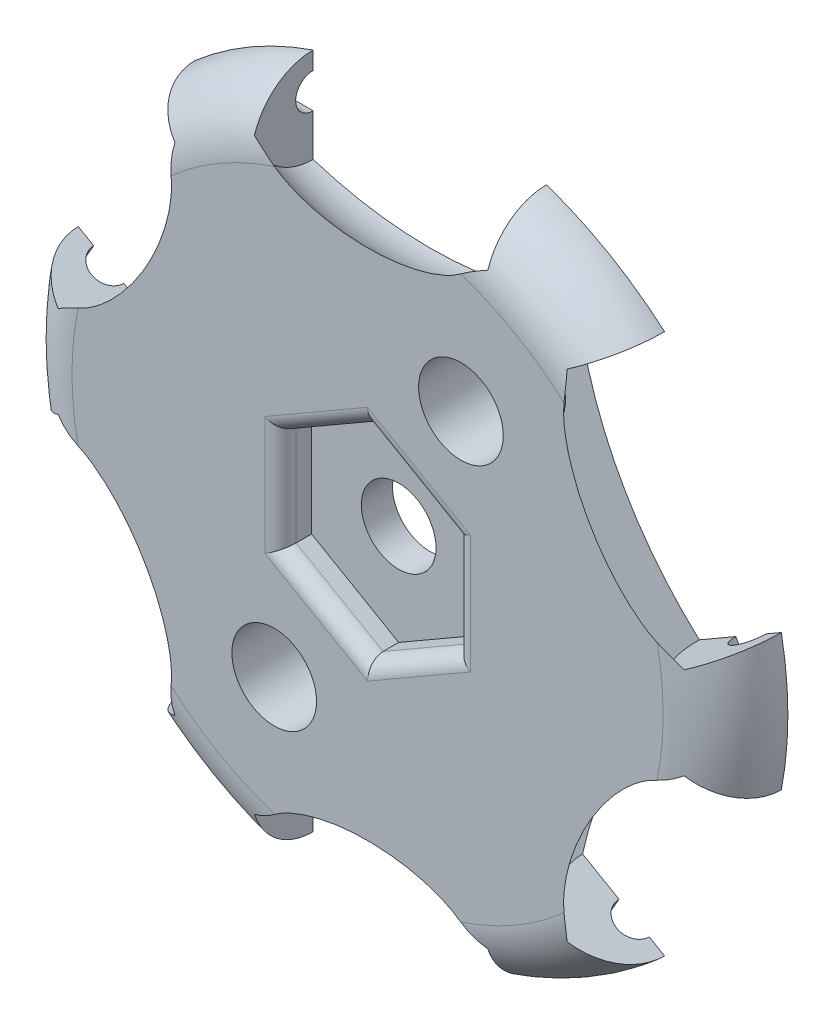
SolidWorks part; units mm, degrees
ref_plane "Front Plane" through (0, 0, 0) normal (0, 0, 1) x (1, 0, 0)
ref_plane "Top Plane" through (0, 0, 0) normal (0, 1, 0) x (1, 0, 0)
ref_plane "Right Plane" through (0, 0, 0) normal (1, 0, 0) x (0, 0, -1)
sketch "Sketch1" plane through (0, 0, 0) normal (0, 0, 1) x (1, 0, 0)
  circle A0 centre (0, 0) radius 18.2626
  dimension "D1" = 36.5252
extrude "Boss-Extrude1" add sketch "Sketch1" along normal blind 3.175
fillet "Fillet1" radius 3.1852 1 edges at (18.2626, 0, 3.175)
sketch "Sketch2" plane through (0, 0, 3.175) normal (0, 0, 1) x (1, 0, 0)
  line L0 (-4.7625, -8.2489) -> (4.7625, 8.2489) construction
  line L1 (0, 0) -> (0, 6.4682) construction
  circle A0 centre (4.7625, 8.2489) radius 2.159
  circle A1 centre (-4.7625, -8.2489) radius 2.159
  circle A4 centre (0, 0) radius 1.905
  point P9 (0, 0)
  dimension "D2" = 4.318
  dimension "D4" = 3.81
  dimension "D1" = 9.525
  dimension "D5" = 30
  dimension "D3" = 2
extrude "Cut-Extrude1" cut sketch "Sketch2" against normal through all
sketch "Sketch5" plane through (0, 0, 0) normal (0, 0, 1) x (1, 0, 0)
  line L0 (-5.9531, 15.4686) -> (5.9531, 15.4686)
  line L1 (5.9531, 15.4686) -> (5.9531, 18.5033)
  line L2 (-5.9531, 15.4686) -> (-5.9531, 18.5033)
  line L3 (-5.9531, 15.4686) -> (-8.5086, 15.4686) construction
  arc A0 (-5.9531, 18.5033) -> (5.9531, 18.5033) centre (0, 0) cw
  circle A1 centre (0, 0) radius 18.2626 construction
  point P5 (0, 15.4686)
  point P9 (0, 19.4373)
  dimension "D1" = 11.9062
  dimension "D2" = 15.4686
  dimension "D3" = 7.9375
revolve "Cut-Revolve1" cut sketch "Sketch5" angle 360 about L3
sketch "Sketch6" plane through (0, 0, 0) normal (1, 0, 0) x (0, 0, -1)
  line L0 (0, -18.2626) -> (0, 17.2651) construction
  circle A0 centre (0, 15.4686) radius 0.889
  arc A1 (-2.9966, 14.9895) -> (0, 12.4339) centre (0, 15.4686) ccw construction
  dimension "D1" = 1.778
extrude "Cut-Extrude2" cut sketch "Sketch6" against normal mid plane 15.875
pattern_circular "CirPattern1" count 6 over 360 about axis through (0, 0, 0) along (0, 0, 1) of "Cut-Revolve1", "Cut-Extrude2"
sketch "Sketch8" plane through (0, 0, 3.175) normal (0, 0, 1) x (1, 0, 0)
  line L1 (0, 5.1326) -> (-4.445, 2.5663)
  line L2 (-4.445, 2.5663) -> (-4.445, -2.5663)
  line L3 (-4.445, -2.5663) -> (0, -5.1326)
  line L4 (0, -5.1326) -> (4.445, -2.5663)
  line L5 (4.445, -2.5663) -> (4.445, 2.5663)
  line L6 (4.445, 2.5663) -> (0, 5.1326)
  circle A0 centre (0, 0) radius 4.445 construction
  dimension "D1" = 8.89
extrude "Cut-Extrude4" cut sketch "Sketch8" against normal blind 1.5875
fillet "Fillet2" radius 0.7937 6 edges at (-2.2225, 3.8495, 3.175) (-4.445, 0, 3.175) (-2.2225, -3.8495, 3.175) (2.2225, -3.8495, 3.175) (4.445, 0, 3.175) (2.2225, 3.8495, 3.175)
